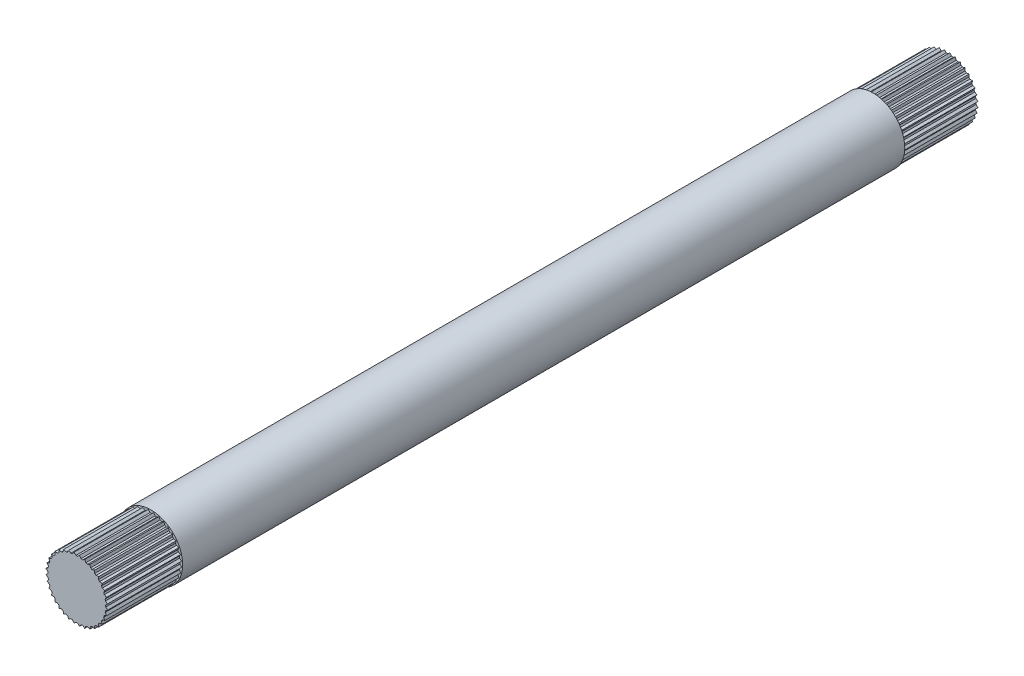
SolidWorks part; units mm, degrees
material "AISI 1015 Steel, Cold Drawn (SS)"
ref_plane "X-Y Datum" through (0, 0, 0) normal (0, 0, 1) x (1, 0, 0)
ref_plane "X-Z Datum" through (0, 0, 0) normal (0, 1, 0) x (1, 0, 0)
ref_plane "Y-Z Datum" through (0, 0, 0) normal (1, 0, 0) x (0, 0, -1)
sketch "Sketch9" plane through (0, 0, 0) normal (0, 1, 0) x (1, 0, 0)
  line L0 (16.002, 0) -> (0, 0)
  line L1 (0, 0) -> (0, -304.8)
  line L2 (0, -304.8) -> (-72.2493, -440.6812)
  dimension "D1" = 153.895
  dimension "D2" = 28
  dimension "D3" = 304.8
  dimension "D5" = 16.002
sketch "Sketch5" plane through (0, 0, 0) normal (0, 1, 0) x (1, 0, 0)
  line L0 (7.9375, -283.21) -> (7.9375, -22.1615)
  line L1 (7.9375, -22.1615) -> (9.525, -22.1615)
  line L2 (9.525, -22.1615) -> (9.525, -283.21)
  line L3 (9.525, -283.21) -> (7.9375, -283.21)
  line L5 (16.002, 0) -> (0, 0) construction
  line L6 (0, 0) -> (0, -304.8) construction
  line L7 (0, -304.8) -> (9.525, -304.8) construction
  line L8 (12.5602, -285.55) -> (0, -285.55) construction
  dimension "D1" = 1.5875
  dimension "D2" = 22.1615
  dimension "D3" = 7.9375
  dimension "D4" = 19.25
  dimension "D5" = 21.59
revolve "Revolve2" add sketch "Sketch5" angle 360 about L1
sketch "Sketch6" plane through (0, 0, 0) normal (0, 1, 0) x (1, 0, 0)
  circle A0 centre (0, -33.1635) radius 1.5875 construction
  circle A1 centre (0, -33.1635) radius 1.5875
sketch "Sketch7" plane through (0, 0, 0) normal (1, 0, 0) x (0, 0, -1)
  circle A2 centre (-39.196, 0) radius 1.5875
  circle A4 centre (-39.196, 0) radius 1.5875 construction
extrude "Cut-Extrude5" [suppressed] cut sketch "Sketch7" against normal through all both and the other way through all
extrude "Cut-Extrude6" [suppressed] cut sketch "Sketch6" against normal through all both and the other way through all
sketch "Sketch8" plane through (0, 0, 0) normal (0, 0, 1) x (1, 0, 0)
  line L0 (9.2357, -0.808) -> (8.6817, -0.254)
  line L1 (8.6817, -0.254) -> (8.6817, 0.254)
  line L2 (8.6817, 0.254) -> (9.2357, 0.808)
  line L3 (8.6817, 0) -> (0, 0) construction
  line L4 (8.9551, -2.3995) -> (8.5057, -1.7577)
  line L5 (8.5057, -1.7577) -> (8.5939, -1.2574)
  line L6 (8.5939, -1.2574) -> (9.2357, -0.808)
  line L7 (8.4024, -3.9181) -> (8.0713, -3.208)
  line L8 (8.0713, -3.208) -> (8.245, -2.7306)
  line L9 (8.245, -2.7306) -> (8.9551, -2.3995)
  line L10 (7.5944, -5.3176) -> (7.3916, -4.5608)
  line L11 (7.3916, -4.5608) -> (7.6456, -4.1209)
  line L12 (7.6456, -4.1209) -> (8.4024, -3.9181)
  line L13 (6.5556, -6.5556) -> (6.4873, -5.7751)
  line L14 (6.4873, -5.7751) -> (6.8138, -5.3859)
  line L15 (6.8138, -5.3859) -> (7.5944, -5.3176)
  line L16 (5.3176, -7.5944) -> (5.3859, -6.8138)
  line L17 (5.3859, -6.8138) -> (5.7751, -6.4873)
  line L18 (5.7751, -6.4873) -> (6.5556, -6.5556)
  line L19 (3.9181, -8.4024) -> (4.1209, -7.6456)
  line L20 (4.1209, -7.6456) -> (4.5608, -7.3916)
  line L21 (4.5608, -7.3916) -> (5.3176, -7.5944)
  line L22 (2.3995, -8.9551) -> (2.7306, -8.245)
  line L23 (2.7306, -8.245) -> (3.208, -8.0713)
  line L24 (3.208, -8.0713) -> (3.9181, -8.4024)
  line L25 (0.808, -9.2357) -> (1.2574, -8.5939)
  line L26 (1.2574, -8.5939) -> (1.7577, -8.5057)
  line L27 (1.7577, -8.5057) -> (2.3995, -8.9551)
  line L28 (-0.808, -9.2357) -> (-0.254, -8.6817)
  line L29 (-0.254, -8.6817) -> (0.254, -8.6817)
  line L30 (0.254, -8.6817) -> (0.808, -9.2357)
  line L31 (-2.3995, -8.9551) -> (-1.7577, -8.5057)
  line L32 (-1.7577, -8.5057) -> (-1.2574, -8.5939)
  line L33 (-1.2574, -8.5939) -> (-0.808, -9.2357)
  line L34 (-3.9181, -8.4024) -> (-3.208, -8.0713)
  line L35 (-3.208, -8.0713) -> (-2.7306, -8.245)
  line L36 (-2.7306, -8.245) -> (-2.3995, -8.9551)
  line L37 (-5.3176, -7.5944) -> (-4.5608, -7.3916)
  line L38 (-4.5608, -7.3916) -> (-4.1209, -7.6456)
  line L39 (-4.1209, -7.6456) -> (-3.9181, -8.4024)
  line L40 (-6.5556, -6.5556) -> (-5.7751, -6.4873)
  line L41 (-5.7751, -6.4873) -> (-5.3859, -6.8138)
  line L42 (-5.3859, -6.8138) -> (-5.3176, -7.5944)
  line L43 (-7.5944, -5.3176) -> (-6.8138, -5.3859)
  line L44 (-6.8138, -5.3859) -> (-6.4873, -5.7751)
  line L45 (-6.4873, -5.7751) -> (-6.5556, -6.5556)
  line L46 (-8.4024, -3.9181) -> (-7.6456, -4.1209)
  line L47 (-7.6456, -4.1209) -> (-7.3916, -4.5608)
  line L48 (-7.3916, -4.5608) -> (-7.5944, -5.3176)
  line L49 (-8.9551, -2.3995) -> (-8.245, -2.7306)
  line L50 (-8.245, -2.7306) -> (-8.0713, -3.208)
  line L51 (-8.0713, -3.208) -> (-8.4024, -3.9181)
  line L52 (-9.2357, -0.808) -> (-8.5939, -1.2574)
  line L53 (-8.5939, -1.2574) -> (-8.5057, -1.7577)
  line L54 (-8.5057, -1.7577) -> (-8.9551, -2.3995)
  line L55 (-9.2357, 0.808) -> (-8.6817, 0.254)
  line L56 (-8.6817, 0.254) -> (-8.6817, -0.254)
  line L57 (-8.6817, -0.254) -> (-9.2357, -0.808)
  line L58 (-8.9551, 2.3995) -> (-8.5057, 1.7577)
  line L59 (-8.5057, 1.7577) -> (-8.5939, 1.2574)
  line L60 (-8.5939, 1.2574) -> (-9.2357, 0.808)
  line L61 (-8.4024, 3.9181) -> (-8.0713, 3.208)
  line L62 (-8.0713, 3.208) -> (-8.245, 2.7306)
  line L63 (-8.245, 2.7306) -> (-8.9551, 2.3995)
  line L64 (-7.5944, 5.3176) -> (-7.3916, 4.5608)
  line L65 (-7.3916, 4.5608) -> (-7.6456, 4.1209)
  line L66 (-7.6456, 4.1209) -> (-8.4024, 3.9181)
  line L67 (-6.5556, 6.5556) -> (-6.4873, 5.7751)
  line L68 (-6.4873, 5.7751) -> (-6.8138, 5.3859)
  line L69 (-6.8138, 5.3859) -> (-7.5944, 5.3176)
  line L70 (-5.3176, 7.5944) -> (-5.3859, 6.8138)
  line L71 (-5.3859, 6.8138) -> (-5.7751, 6.4873)
  line L72 (-5.7751, 6.4873) -> (-6.5556, 6.5556)
  line L73 (-3.9181, 8.4024) -> (-4.1209, 7.6456)
  line L74 (-4.1209, 7.6456) -> (-4.5608, 7.3916)
  line L75 (-4.5608, 7.3916) -> (-5.3176, 7.5944)
  line L76 (-2.3995, 8.9551) -> (-2.7306, 8.245)
  line L77 (-2.7306, 8.245) -> (-3.208, 8.0713)
  line L78 (-3.208, 8.0713) -> (-3.9181, 8.4024)
  line L79 (-0.808, 9.2357) -> (-1.2574, 8.5939)
  line L80 (-1.2574, 8.5939) -> (-1.7577, 8.5057)
  line L81 (-1.7577, 8.5057) -> (-2.3995, 8.9551)
  line L82 (0.808, 9.2357) -> (0.254, 8.6817)
  line L83 (0.254, 8.6817) -> (-0.254, 8.6817)
  line L84 (-0.254, 8.6817) -> (-0.808, 9.2357)
  line L85 (2.3995, 8.9551) -> (1.7577, 8.5057)
  line L86 (1.7577, 8.5057) -> (1.2574, 8.5939)
  line L87 (1.2574, 8.5939) -> (0.808, 9.2357)
  line L88 (3.9181, 8.4024) -> (3.208, 8.0713)
  line L89 (3.208, 8.0713) -> (2.7306, 8.245)
  line L90 (2.7306, 8.245) -> (2.3995, 8.9551)
  line L91 (5.3176, 7.5944) -> (4.5608, 7.3916)
  line L92 (4.5608, 7.3916) -> (4.1209, 7.6456)
  line L93 (4.1209, 7.6456) -> (3.9181, 8.4024)
  line L94 (6.5556, 6.5556) -> (5.7751, 6.4873)
  line L95 (5.7751, 6.4873) -> (5.3859, 6.8138)
  line L96 (5.3859, 6.8138) -> (5.3176, 7.5944)
  line L97 (7.5944, 5.3176) -> (6.8138, 5.3859)
  line L98 (6.8138, 5.3859) -> (6.4873, 5.7751)
  line L99 (6.4873, 5.7751) -> (6.5556, 6.5556)
  line L100 (8.4024, 3.9181) -> (7.6456, 4.1209)
  line L101 (7.6456, 4.1209) -> (7.3916, 4.5608)
  line L102 (7.3916, 4.5608) -> (7.5944, 5.3176)
  line L103 (8.9551, 2.3995) -> (8.245, 2.7306)
  line L104 (8.245, 2.7306) -> (8.0713, 3.208)
  line L105 (8.0713, 3.208) -> (8.4024, 3.9181)
  line L106 (9.2357, 0.808) -> (8.5939, 1.2574)
  line L107 (8.5939, 1.2574) -> (8.5057, 1.7577)
  line L108 (8.5057, 1.7577) -> (8.9551, 2.3995)
  circle A0 centre (0, 0) radius 12.7
  circle A1 centre (0, 0) radius 9.271 construction
  circle A2 centre (0, 0) radius 8.6854 construction
  point P153 (0, 0)
  dimension "D1" = 25.4
  dimension "D4" = 18.542
  dimension "D6" = 17.3708
  dimension "D2" = 0.508
  dimension "D3" = 135
  dimension "D5" = 36
extrude "Cut-Extrude7" cut sketch "Sketch8" against normal blind 22.225 from surface starting at face at (-9.525, 0, 283.21)
ref_plane "Plane1" through (0, 0, 47.5615) normal (0, 0, -1) x (-1, 0, 0)
sketch "Sketch10" plane through (0, 0, 47.5615) normal (0, 0, -1) x (-1, 0, 0)
  circle A0 centre (0, 0) radius 7.9375
  dimension "D1" = 15.875
extrude "Boss-Extrude1" add sketch "Sketch10" against normal up to surface (235.6485 mm away) up to face at (-7.9375, 0, 283.21)
sketch "Sketch11" plane through (0, 0, 22.1615) normal (0, 0, -1) x (-1, 0, 0)
  line L0 (0, 9.525) -> (13.3548, 9.525) construction
  line L1 (0, 9.525) -> (0, 15.4312) construction
  line L2 (-9.525, 0) -> (-9.525, 9.1744) construction
  line L3 (-9.525, 0) -> (-16.674, 0) construction
  circle A0 centre (0, 0) radius 9.525 construction
  point P0 (0, 9.525)
  point P1 (-9.525, 0)
extrude "Cut-Extrude8" cut sketch "Sketch8<2>" along normal blind 44.4119
sketch "Sketch8<2>" plane through (0, 0, 0) normal (0, 0, 1) x (1, 0, 0) same geometry as "Sketch8"
